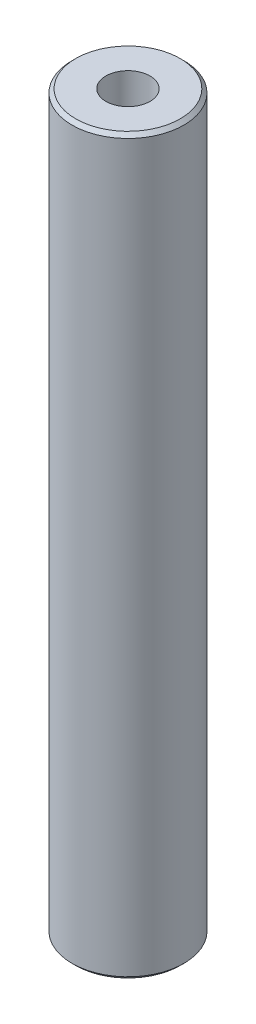
SolidWorks part; units mm, degrees
ref_plane "Front Plane" through (0, 0, 0) normal (0, 0, 1) x (1, 0, 0)
ref_plane "Top Plane" through (0, 0, 0) normal (0, 1, 0) x (1, 0, 0)
ref_plane "Right Plane" through (0, 0, 0) normal (1, 0, 0) x (0, 0, -1)
sketch "Sketch1" plane through (0, 0, 0) normal (0, 1, 0) x (1, 0, 0)
  circle A0 centre (0, 0) radius 15
  dimension "SHAFT_OD" = 30
extrude "Boss-Extrude1" add sketch "Sketch1" along normal blind 196.7768
sketch "Sketch2" plane through (0, 0, 0) normal (0, 1, 0) x (1, 0, 0)
  circle A0 centre (0, 0) radius 5.9251
  dimension "BORE_D" = 11.8501
extrude "Cut-Extrude1" cut sketch "Sketch2" along normal through all
chamfer "Chamfer1" distance 0.9751 angle 45 2 edges at (0, 196.7768, 15) (0, 0, 15)
